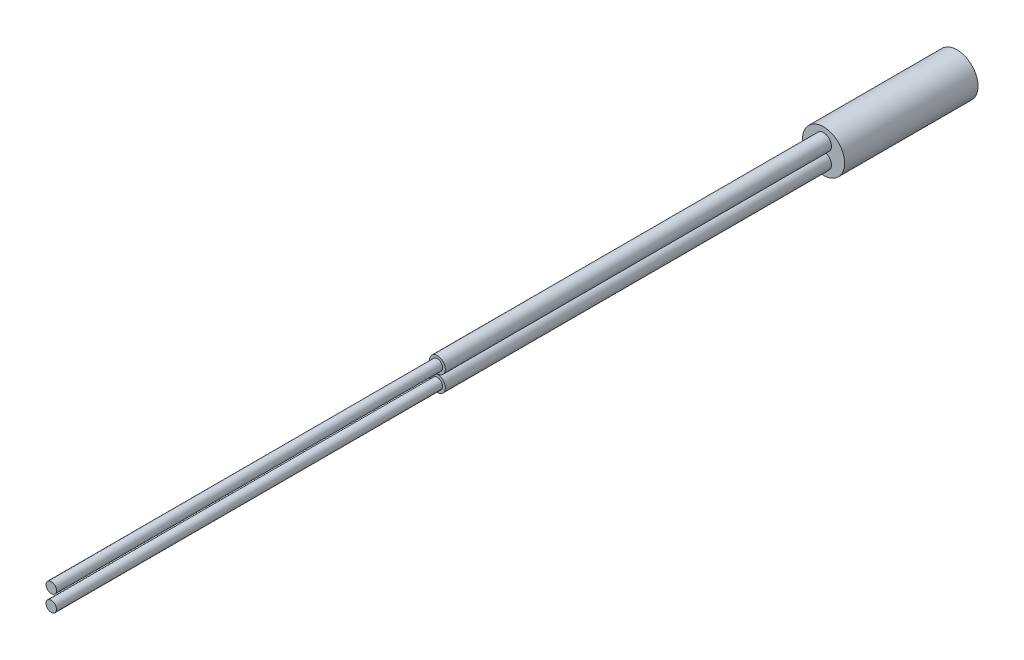
SolidWorks part; units mm, degrees
material "acero"
ref_plane "Alzado" through (0, 0, 0) normal (0, 0, 1) x (1, 0, 0)
ref_plane "Planta" through (0, 0, 0) normal (0, 1, 0) x (1, 0, 0)
ref_plane "Vista lateral" through (0, 0, 0) normal (1, 0, 0) x (0, 0, -1)
sketch "Croquis1" plane through (0, 0, 0) normal (0, 0, 1) x (1, 0, 0)
  circle A0 centre (0, 0) radius 3
  dimension "D1" = 6
extrude "Saliente-Extruir1" add sketch "Croquis1" along normal blind 18
ref_plane "Plano1" through (0, 0.5, 0) normal (0, -1, 0) x (-1, 0, 0)
ref_plane "Plano2" through (0, -9.5, 0) normal (0, -1, 0) x (-1, 0, 0)
ref_plane "Plano3" through (-23.0763, 0, 10.7606) normal (-0.9063, 0, 0.4226) x (0.4226, 0, 0.9063)
sketch3d "Croquis3D1"
  line L0 (0, 0, 18) -> (0, 0, 21)
  line L1 (0, 0, 18) -> (0, 0, 0) construction
  line L2 (-17.166, -4.6752, 23.4353) -> (-17.166, -8.5854, 23.4353)
  line L3 (-6.75, -14.9111, 10) -> (-6.75, 16.5741, 10) construction
  spline S0 degree 3 poles (0, 0, 21) (0, 0, 27.5004) (-12.019, 3.2907, 25.754) (-17.166, -2.2029, 23.4353) (-17.166, -4.6752, 23.4353) knots 0 0 0 0 0.663423 1 1 1 1
  dimension "D1" = 17
  dimension "D2" = 3
sketch "Croquis2" plane through (0, 0, 18) normal (0, 0, 1) x (1, 0, 0)
  circle A0 centre (0, 0) radius 0.8 construction
  circle A1 centre (-0.8, 0) radius 0.75
  circle A2 centre (0.8, 0) radius 0.75
  dimension "D1" = 1.6
  dimension "D2" = 1.5
sweep "Barrer1" [suppressed] add profiles "Croquis2" path "Croquis3D1"
extrude "Saliente-Extruir2" add sketch "Croquis1<2>" along normal blind 21.5 and the other way blind 1.5
sketch "Croquis1<2>" plane through (0, 0, 0) normal (0, 0, 1) x (1, 0, 0) same geometry as "Croquis1"
sketch "Croquis3" plane through (0, 0, -1.5) normal (0, 0, -1) x (-1, 0, 0)
  circle A0 centre (0, 0) radius 3
  dimension "D1" = 6
extrude "Cortar-Extruir1" cut sketch "Croquis3" against normal blind 4
sketch "Croquis4" plane through (0, 0, 0) normal (1, 0, 0) x (0, 0, -1)
  line L0 (-18.6464, 0) -> (-2.5, 0) construction
  line L1 (-2.5, -3) -> (-2.5, 3) construction
  line L2 (-2.5, 0) -> (8.1511, 15.6197) construction
  dimension "D1" = 34.29
sketch3d "Croquis3D4"
  line L0 (0, 0, 2.5) -> (-18.9322, 0, 2.5) construction
ref_plane "Plano4" through (0, 1.1637, 1.7065) normal (0, -0.5634, -0.8262) x (-1, 0, 0)
sketch3d "Croquis3D3" [suppressed]
  line L0 (-1.9716, 13.6377, 26.3138) -> (-2.2072, 8.1317, 30.0679)
  line L1 (-5.6206, 5.0135, 32.2682) -> (-41.5, -3.146, 34.1262)
  line L2 (-47.8249, -2.5398, 38.3697) -> (-47.8249, -22.8208, 52.1977)
  line L3 (-43.8249, -26.1257, 54.4511) -> (-27.8372, -26.1257, 54.4511)
  line L4 (-41, -0.2448, 33.0559) -> (-27.23, 0.0992, 33.3873)
  line L5 (-27.23, 0.0992, 33.3873) -> (-27.23, 3.5226, 33.3873)
  line L6 (-27.23, 3.5226, 33.3873) -> (-1.9922, 3.5226, 33.3873)
ref_plane "Plano5" through (0, 16.9384, 24.84) normal (0, -0.5634, -0.8262) x (-1, 0, 0)
sketch "Croquis6" plane through (0, 16.9384, 24.84) normal (0, -0.5634, -0.8262) x (-1, 0, 0)
  line L0 (0, -15.6127) -> (0, -12.1127) construction
  line L1 (22, -19.1127) -> (22, -15.6127)
  line L4 (22, -15.6127) -> (0, -15.6127)
  line L5 (47.5, -19.1127) -> (22, -19.1127)
  line L6 (47.5, -19.1127) -> (47.5, -50.6127)
  line L7 (47.5, -50.6127) -> (33.5, -50.6127)
  ellipse E0 centre (0, -12.1127) end of major axis (-3, -12.1127) minor radius 2.4786 construction
  dimension "D1" = 38.5
  dimension "D2" = 47.5
  dimension "D3" = 7
  dimension "D4" = 3.5
  dimension "D5" = 22
  dimension "D6" = 14
sketch3d "Croquis3D5"
  line L0 (0, 0, 21.5) -> (0, 4.0392, 33.6359) construction
  line L1 (0, 0, 21.5) -> (0, 0, 2.5) construction
  line L2 (-22, 3.2001, 34.2081) -> (-21.2499, 4.0392, 33.6359) construction
  line L3 (-47.5, -24.8777, 53.3543) -> (-33.5, -24.8777, 53.3543) construction
  line L4 (-47.5, 1.1475, 35.6078) -> (-47.5, -24.8777, 53.3543) construction
  line L5 (-44.5, -24.8777, 53.3543) -> (-47.5, -22.3991, 51.6641) construction
  line L6 (-46.4717, -0.2698, 36.5742) -> (-45.5, 1.1475, 35.6078) construction
  line L7 (-47.5, 1.1475, 35.6078) -> (-22, 1.1475, 35.6078) construction
  line L8 (-22, 1.1475, 35.6078) -> (-22, 4.0392, 33.6359) construction
  line L9 (-22.8792, 1.1475, 35.6078) -> (-22, 1.873, 35.113) construction
  line L10 (-22, 4.0392, 33.6359) -> (0, 4.0392, 33.6359) construction
  line L11 (-2, 4.0392, 33.6359) -> (0, 3.4076, 31.7383) construction
  arc A0 (-42.3787, -24.8777, 53.3543) -> (-47.5, -20.6465, 50.469) centre (-42.3787, -20.6465, 50.469) cw
  arc A1 (-47.5, -2.1436, 37.852) -> (-43.5165, 1.1475, 35.6078) centre (-43.5165, -2.1436, 37.852) cw
  arc A2 (-23.5, 1.1475, 35.6078) -> (-22, 2.3868, 34.7627) centre (-23.5, 2.3868, 34.7627) cw
  arc A4 (-3.4142, 4.0392, 33.6359) -> (0, 2.961, 30.3964) centre (-3.4142, 2.961, 30.3964) cw
  arc A5 (-22, 2.7999, 34.481) -> (-20.5, 4.0392, 33.6359) centre (-20.5, 2.7999, 34.481) cw
  point P7 (-42.3787, -23.5317, 46.2378)
  point P16 (-46, -23.6384, 52.5092)
  point P25 (-43.5165, -4.3879, 34.5608)
  point P27 (-45.9859, 0.4389, 36.091)
  point P29 (-23.5, 3.2319, 36.002)
  point P31 (-22.4396, 1.5102, 35.3604)
  point P44 (-20.5, 1.9548, 33.2417)
  point P46 (-21.625, 3.6196, 33.922)
  point P51 (-3.4142, 6.2005, 29.3182)
  point P53 (-1, 3.7234, 32.6871)
  dimension "D5" = 1.5
  dimension "D2" = 3
  dimension "D11" = 3
  dimension "D3" = 2
  dimension "D4" = 2
  dimension "D7" = 1.5
  dimension "D9" = 2
  dimension "D10" = 2
sketch3d "Croquis3D7"
  line L0 (-47.5, -24.8777, 53.3543) -> (-33.5, -24.8777, 53.3543) construction
  line L1 (-47.5, 1.1475, 35.6078) -> (-47.5, -24.8777, 53.3543) construction
  line L2 (-47.5, 1.1475, 35.6078) -> (-22, 1.1475, 35.6078) construction
  line L3 (-22, 1.1475, 35.6078) -> (-22, 4.0392, 33.6359) construction
  line L4 (-22, 4.0392, 33.6359) -> (0, 4.0392, 33.6359) construction
  line L5 (0, 0, 21.5) -> (0, 4.0392, 33.6359) construction
  line L6 (-42.3787, -24.8777, 53.3543) -> (-33.5, -24.8777, 53.3543)
  line L7 (-47.5, -2.1436, 37.852) -> (-47.5, -20.6465, 50.469)
  line L8 (-43.5165, 1.1475, 35.6078) -> (-23.5, 1.1475, 35.6078)
  line L9 (-22, 2.3868, 34.7627) -> (-22, 2.7999, 34.481)
  line L10 (-20.5, 4.0392, 33.6359) -> (-3.4142, 4.0392, 33.6359)
  line L11 (0, 0, 21.5) -> (0, 2.961, 30.3964)
  arc A0 (-42.3787, -24.8777, 53.3543) -> (-47.5, -20.6465, 50.469) centre (-42.3787, -20.6465, 50.469) ccw construction
  arc A1 (-47.5, -2.1436, 37.852) -> (-43.5165, 1.1475, 35.6078) centre (-43.5165, -2.1436, 37.852) ccw construction
  arc A2 (-23.5, 1.1475, 35.6078) -> (-22, 2.3868, 34.7627) centre (-23.5, 2.3868, 34.7627) ccw construction
  arc A4 (-3.4142, 4.0392, 33.6359) -> (0, 2.961, 30.3964) centre (-3.4142, 2.961, 30.3964) ccw construction
  arc A5 (-42.3787, -24.8777, 53.3543) -> (-47.5, -20.6465, 50.469) centre (-42.3787, -20.6465, 50.469) ccw
  arc A6 (-47.5, -2.1436, 37.852) -> (-43.5165, 1.1475, 35.6078) centre (-43.5165, -2.1436, 37.852) ccw
  arc A7 (-23.5, 1.1475, 35.6078) -> (-22, 2.3868, 34.7627) centre (-23.5, 2.3868, 34.7627) ccw
  arc A8 (-22, 2.7999, 34.481) -> (-20.5, 4.0392, 33.6359) centre (-20.5, 2.7999, 34.481) ccw construction
  arc A9 (-3.4142, 4.0392, 33.6359) -> (0, 2.961, 30.3964) centre (-3.4142, 2.961, 30.3964) ccw
  arc A10 (-22, 2.7999, 34.481) -> (-20.5, 4.0392, 33.6359) centre (-20.5, 2.7999, 34.481) ccw
  point P5 (-42.3787, -23.5317, 46.2378)
  point P10 (-43.5165, -4.3879, 34.5608)
  point P15 (-23.5, 3.2319, 36.002)
  point P20 (-20.5, 1.9548, 33.2417)
  point P25 (-3.4142, 6.2005, 29.3182)
  point P27 (-42.3787, -23.5317, 46.2378)
  point P28 (-43.5165, -4.3879, 34.5608)
  point P29 (-23.5, 3.2319, 36.002)
  point P31 (-3.4142, 6.2005, 29.3182)
  point P32 (-20.5, 1.9548, 33.2417)
ref_plane "Plano6" through (-33.5, -24.8777, 53.3543) normal (1, 0, 0) x (0, 0, -1)
sketch "Croquis7" plane through (-33.5, -24.8777, 53.3543) normal (1, 0, 0) x (0, 0, -1)
  line L0 (0.9708, -0.662) -> (-0.9708, 0.662) construction
  line L1 (17.7465, 26.0252) -> (0, 0) construction
  circle A0 centre (-0.9708, 0.662) radius 1.125
  circle A1 centre (0.9708, -0.662) radius 1.125
  dimension "D1" = 2.25
  dimension "D2" = 0.1
  dimension "D3" = 4.6
sweep "Barrer2" [suppressed] add profiles "Croquis7" path "Croquis3D7"
sketch "Croquis8" [suppressed] plane through (-33.5, 0, 0) normal (1, 0, 0) x (0, 0, -1)
  circle A0 centre (-54.6664, -23.983) radius 0.75
  circle A1 centre (-52.7248, -25.3069) radius 0.75
  dimension "D1" = 1.5
sketch3d "Croquis3D8" [suppressed]
  line L0 (-33.5, -25.3069, 52.7248) -> (-32.5, -25.3069, 52.7248)
  line L1 (-31.5, -25.8805, 51.9057) -> (-31.5, -26.6156, 50.8559) construction
  line L2 (-31.5, -25.3069, 52.7248) -> (-31.5, -25.3069, 45.2282) construction
  arc A0 (-32.5, -25.3069, 52.7248) -> (-31.5, -25.8805, 51.9057) centre (-32.5, -25.8805, 51.9057) ccw
  point P7 (-31.5, -25.3069, 52.7248)
  point P9 (-32.5, -25.0614, 51.3321)
  dimension "D3" = 1
  dimension "D1" = 2
  dimension "D2" = 1
  dimension "D5" = 1
  dimension "D4" = 35
sweep "Barrer3" [suppressed] add profiles "Croquis8" path "Croquis3D8"
sketch "Croquis9" plane through (0, 0, 21.5) normal (0, 0, 1) x (1, 0, 0)
  line L0 (0, 1.15) -> (0, -1.15) construction
  circle A0 centre (0, -1.15) radius 1.125
  circle A1 centre (0, 1.15) radius 1.125
  dimension "D1" = 2.25
  dimension "D2" = 2.3
extrude "Saliente-Extruir3" add sketch "Croquis9" along normal blind 55
sketch "Croquis10" plane through (0, 0, 21.5) normal (0, 0, 1) x (1, 0, 0)
  circle A0 centre (0, -1.15) radius 0.75
  circle A1 centre (0, 1.15) radius 0.75
  circle A2 centre (0, 1.15) radius 1.125 construction
  circle A3 centre (0, -1.15) radius 1.125 construction
  dimension "D1" = 1.5
extrude "Saliente-Extruir4" add sketch "Croquis10" along normal blind 110
